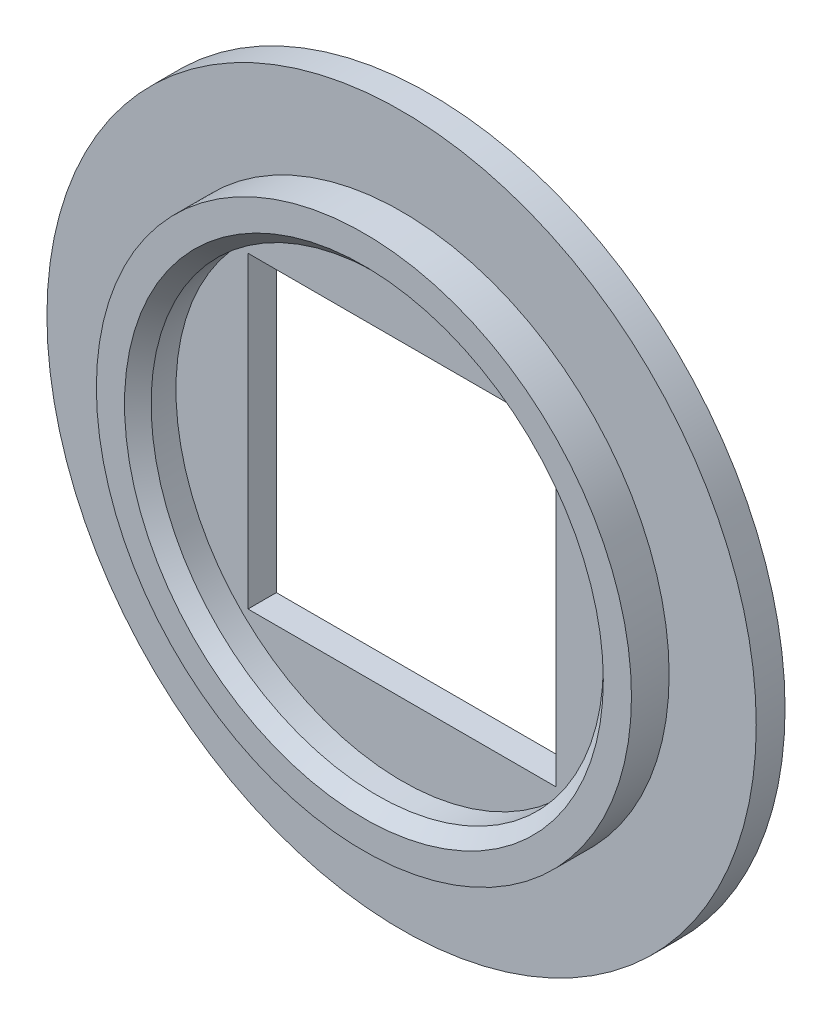
SolidWorks part; units mm, degrees
ref_plane "前视基准面" through (0, 0, 0) normal (0, 0, 1) x (1, 0, 0)
ref_plane "上视基准面" through (0, 0, 0) normal (0, 1, 0) x (1, 0, 0)
ref_plane "右视基准面" through (0, 0, 0) normal (1, 0, 0) x (0, 0, -1)
sketch "草图1" plane through (0, 0, 0) normal (0, 0, 1) x (1, 0, 0)
  circle A0 centre (0, 0) radius 8
extrude "凸台-拉伸1" add sketch "草图1" along normal blind 0.65
sketch "草图2" plane through (0, 0, 0) normal (0, 0, 1) x (1, 0, 0)
  circle A0 centre (0, 0) radius 6.035
  circle A1 centre (0, 0) radius 5.1
extrude "凸台-拉伸2" add sketch "草图2" along normal blind 0.85 from surface starting at face at (8, 0, 0.65)
sketch "草图3" plane through (0, 0, 0) normal (0, 0, 1) x (1, 0, 0)
  circle A0 centre (0, 0) radius 5.1
extrude "切除-拉伸1" cut sketch "草图3" against normal blind 0.01 from surface starting at face at (6.035, 0, 0.65)
sketch "草图4" plane through (0, 0, 0) normal (0, 0, 1) x (1, 0, 0)
  line L16 (-3.475, 3.475) -> (3.475, 3.475)
  line L17 (-3.475, 0) -> (-3.475, 3.475)
  line L18 (-3.475, 0) -> (-3.475, -3.475)
  line L19 (3.475, 3.475) -> (3.475, -3.475)
  line L20 (3.475, -3.475) -> (-3.475, -3.475)
extrude "切除-拉伸2" cut sketch "草图4" along normal up to surface (0.64 mm away) up to face at (5.1, 0, 0.64)
chamfer "倒角1" distance 0.3 angle 45 1 edges at (5.1, 0, 1.5)
